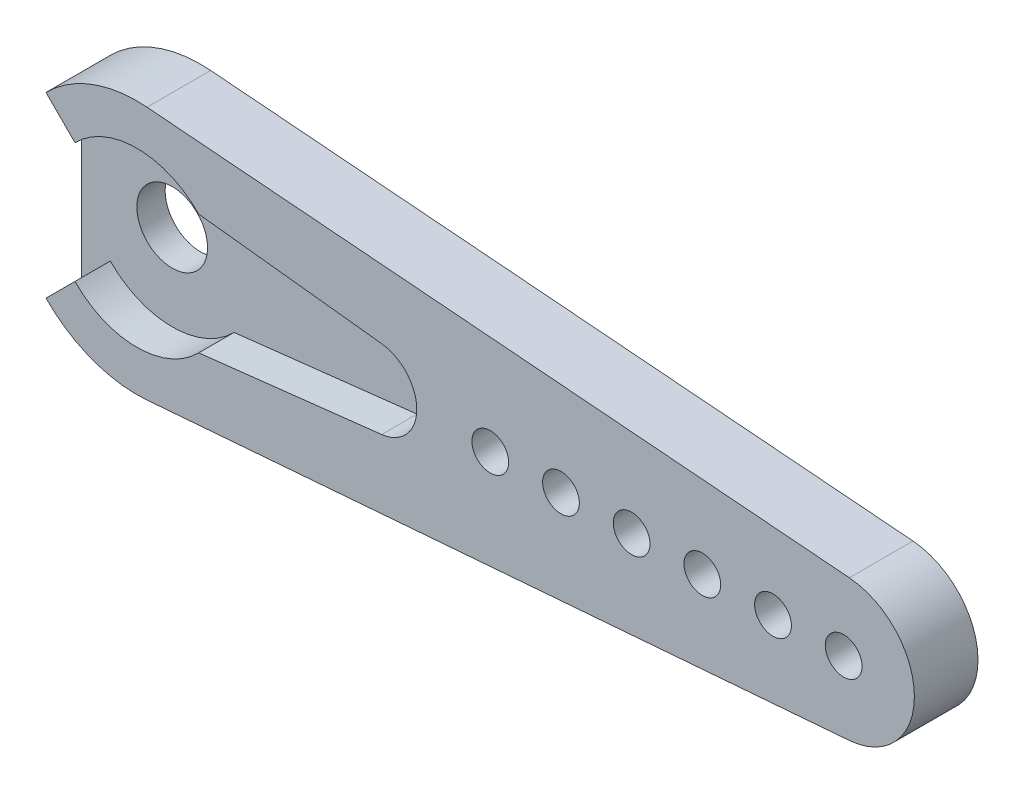
SolidWorks part; units mm, degrees
ref_plane "Front Plane" through (0, 0, 0) normal (0, 0, 1) x (1, 0, 0)
ref_plane "Top Plane" through (0, 0, 0) normal (0, 1, 0) x (1, 0, 0)
ref_plane "Right Plane" through (0, 0, 0) normal (1, 0, 0) x (0, 0, -1)
ref_axis "Axis1" through (58.0713, 0, 0) along (-1, 0, 0)
sketch "Esquisse1" plane through (0, 0, 0) normal (0, 0, 1) x (1, 0, 0)
  line L0 (-4.3758, 4.25) -> (-6.4265, 6.3008)
  line L1 (4.3758, 4.25) -> (17.3156, 2.7822)
  line L2 (17.3156, -2.7822) -> (4.3758, -4.25)
  line L4 (0.72, 8.9712) -> (50.4, 4.984)
  line L5 (0.72, -8.9712) -> (50.4, -4.984)
  line L6 (-4.3758, -4.25) -> (-6.4265, -6.3008)
  arc A0 (4.3758, 4.25) -> (-4.3758, 4.25) centre (0, 0) ccw
  arc A1 (17.3156, -2.7822) -> (17.3156, 2.7822) centre (17, 0) ccw
  arc A2 (4.3758, -4.25) -> (-4.3758, -4.25) centre (0, 0) cw
  arc A3 (-6.4265, 6.3008) -> (0.72, 8.9712) centre (0, 0) cw
  arc A4 (50.4, 4.984) -> (50.4, -4.984) centre (50, 0) cw
  arc A5 (-6.4265, -6.3008) -> (0.72, -8.9712) centre (0, 0) ccw
  dimension "D2" = 6.1
  dimension "D3" = 2.8
  dimension "D6" = 9
  dimension "D8" = 5
  dimension "D1" = 8.5
  dimension "D4" = 17
  dimension "D7" = 50
extrude "Main" add sketch "Esquisse1" along normal blind 2.5
sketch "Esquisse2" plane through (0, 0, 0) normal (0, 0, -1) x (-1, 0, 0)
  line L0 (-0.72, -8.9712) -> (-50.4, -4.984)
  line L1 (-0.72, -8.9712) -> (-50.4, -4.984) construction
  line L3 (-0.72, 8.9712) -> (-50.4, 4.984)
  line L4 (6.4265, -6.3008) -> (6.4265, 6.3008)
  arc A0 (-50.4, 4.984) -> (-50.4, -4.984) centre (-50, 0) ccw construction
  arc A1 (-0.72, -8.9712) -> (6.4265, -6.3008) centre (0, 0) ccw
  circle A2 centre (0, 0) radius 2.5
  arc A3 (6.4265, 6.3008) -> (-0.72, 8.9712) centre (0, 0) ccw
  arc A5 (-50.4, 4.984) -> (-50.4, -4.984) centre (-50, 0) ccw
  arc A6 (-0.72, -8.9712) -> (6.4265, -6.3008) centre (0, 0) ccw construction
  dimension "D1" = 5
extrude "OriginalBracket" add sketch "Esquisse2" along normal blind 2
sketch "Esquisse3" plane through (0, 0, 2.5) normal (0, 0, 1) x (1, 0, 0)
  circle A0 centre (50, 0) radius 1.3
  arc A2 (50.4, -4.984) -> (50.4, 4.984) centre (50, 0) ccw construction
  dimension "D1" = 2.6
extrude "FixingHole" cut sketch "Esquisse3" against normal through all
pattern_linear "LPattern1" count 6 spacing 5 along (-1, 0, 0) of "FixingHole"
